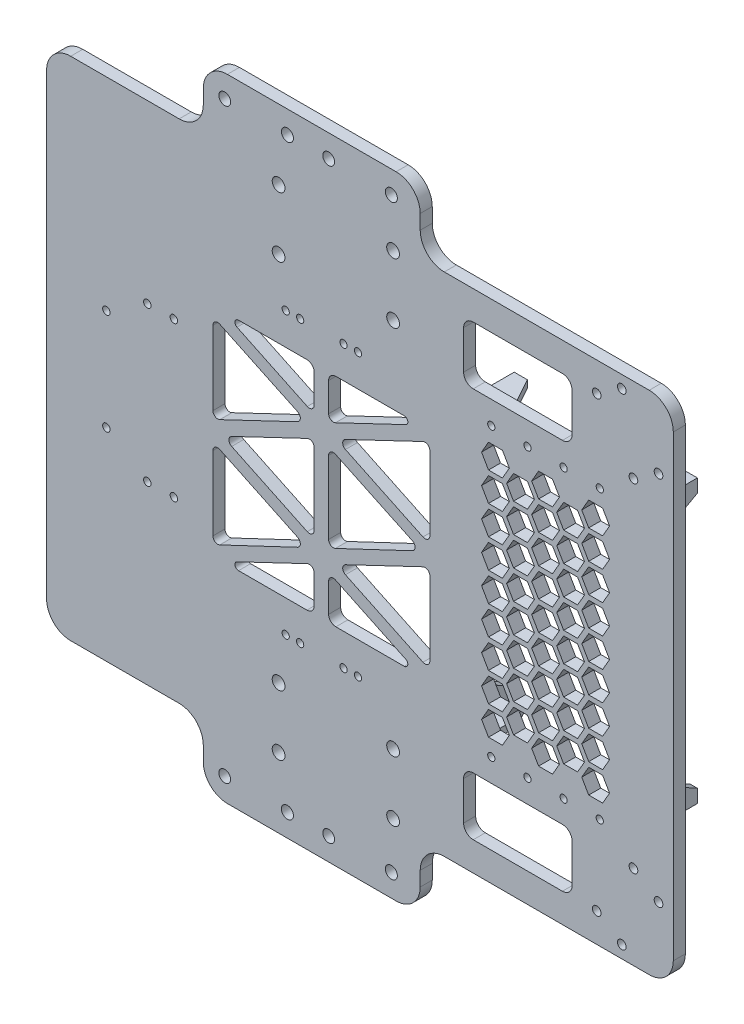
SolidWorks part; units mm, degrees
ref_plane "前视基准面" through (0, 0, 0) normal (0, 0, 1) x (1, 0, 0)
ref_plane "上视基准面" through (0, 0, 0) normal (0, 1, 0) x (1, 0, 0)
ref_plane "右视基准面" through (0, 0, 0) normal (1, 0, 0) x (0, 0, -1)
sketch "草图1" plane through (0, 0, 0) normal (0, 0, 1) x (1, 0, 0)
  line L2 (-130, 95) -> (-130, -95)
  line L3 (-120, -105) -> (-75, -105)
  line L4 (130, 95) -> (130, -95)
  line L5 (126.7518, 102.3765) -> (130, 105) construction
  line L6 (-130, -105) -> (-126.7518, -102.3765) construction
  line L9 (-65, -115) -> (-65, -121)
  line L10 (-55, -131) -> (15, -131)
  line L11 (25, -121) -> (25, -115)
  line L13 (35, -105) -> (120, -105)
  line L14 (126.7518, -102.3765) -> (130, -105) construction
  line L15 (-130, 105) -> (-126.7518, 102.3765) construction
  line L16 (-130, 0) -> (130, 0) construction
  line L17 (35, 105) -> (120, 105)
  line L18 (25, 121) -> (25, 115)
  line L19 (-55, 131) -> (15, 131)
  line L20 (-65, 115) -> (-65, 121)
  line L21 (-120, 105) -> (-75, 105)
  arc A1 (-120, -105) -> (-130, -95) centre (-120, -95) cw
  arc A3 (120, -105) -> (130, -95) centre (120, -95) ccw
  arc A8 (-65, -115) -> (-75, -105) centre (-75, -115) ccw
  arc A9 (25, -115) -> (35, -105) centre (35, -115) cw
  arc A10 (-55, -131) -> (-65, -121) centre (-55, -121) cw
  arc A11 (15, -131) -> (25, -121) centre (15, -121) ccw
  arc A12 (15, 131) -> (25, 121) centre (15, 121) cw
  arc A13 (-55, 131) -> (-65, 121) centre (-55, 121) ccw
  arc A14 (25, 115) -> (35, 105) centre (35, 115) ccw
  arc A15 (-65, 115) -> (-75, 105) centre (-75, 115) cw
  arc A16 (120, 105) -> (130, 95) centre (120, 95) cw
  arc A17 (-120, 105) -> (-130, 95) centre (-120, 95) ccw
  point P0 (0, 0)
  point P40 (25, -105)
  point P45 (25, 105)
  dimension "D2" = 10
  dimension "D3" = 65
  dimension "D4" = 10
  dimension "D5" = 105
  dimension "D7" = 10
  dimension "D8" = 10
  dimension "D10" = 10
  dimension "D12" = 10
  dimension "D13" = 105
  dimension "D18" = 90
  dimension "D19" = 6
extrude "凸台-拉伸1" add sketch "草图1" along normal blind 5
sketch "草图4" plane through (0, 0, 0) normal (0, 0, -1) x (-1, 0, 0)
  line L0 (-39, -47.5) -> (-39, -58.5)
  line L1 (-39, -58.5) -> (-50, -58.5)
  line L2 (-50, -58.5) -> (-50, -55.5)
  line L3 (-50, -55.5) -> (-42, -55.5)
  line L4 (-42, -55.5) -> (-42, -47.5)
  line L5 (-42, -47.5) -> (-39, -47.5)
  line L6 (-130, 0) -> (-25.5592, 0) construction
  line L7 (-130, -95) -> (-130, 95) construction
  line L10 (-130, -95) -> (-130, 95) construction
  dimension "D1" = 11
  dimension "D2" = 11
  dimension "D3" = 3
  dimension "D4" = 3
  dimension "D5" = 80
  dimension "D7" = 55.5
extrude "凸台-拉伸2" add sketch "草图4" along normal blind 20
sketch "草图5" plane through (0, -58.5, 0) normal (0, -1, 0) x (1, 0, 0)
  line L0 (50, -10) -> (44.5, -20)
  line L1 (50, -20) -> (50, 0) construction
  line L2 (50, -20) -> (39, -20) construction
  line L3 (44.5, -20) -> (50, -20)
  line L4 (50, -20) -> (50, -10)
  dimension "D1" = 10
  dimension "D2" = 5.5
extrude "切除-拉伸3" cut sketch "草图5" against normal blind 10
sketch "草图6" plane through (39, 0, 0) normal (-1, 0, 0) x (0, 0, 1)
  line L0 (-20, -53) -> (-10, -47.5)
  line L1 (-20, -58.5) -> (-20, -47.5) construction
  line L2 (-20, -47.5) -> (0, -47.5) construction
  line L3 (-10, -47.5) -> (-20, -47.5)
  line L4 (-20, -47.5) -> (-20, -53)
  dimension "D1" = 10
  dimension "D2" = 5.5
extrude "切除-拉伸4" cut sketch "草图6" against normal blind 10
ref_plane "基准面2" through (77, 0, 0) normal (1, 0, 0) x (0, 0, -1)
mirror "镜向1" about plane through (77, 0, 0) normal (1, 0, 0) of "凸台-拉伸2", "切除-拉伸4", "切除-拉伸3"
mirror "镜向2" about plane through (0, 0, 0) normal (0, 1, 0) of "镜向1"
sketch "草图7" plane through (0, 0, 0) normal (0, 0, -1) x (-1, 0, 0)
  line L4 (-112, -55.5) -> (-104, -55.5) construction
  line L5 (-112, 47.5) -> (-112, 55.5) construction
  line L6 (-112, 55.5) -> (-104, 55.5) construction
  line L7 (-92.013, 36) -> (-94.8997, 41)
  line L8 (-94.8997, 41) -> (-100.6732, 41)
  line L9 (-100.6732, 41) -> (-103.56, 36)
  line L10 (-103.56, 36) -> (-100.6732, 31)
  line L11 (-100.6732, 31) -> (-94.8997, 31)
  line L12 (-94.8997, 31) -> (-92.013, 36)
  line L13 (-77.0019, 36) -> (-97.7865, 36) construction
  line L14 (-74.1151, 31) -> (-71.2284, 36)
  line L15 (-71.2284, 36) -> (-74.1151, 41)
  line L16 (-74.1151, 41) -> (-79.8886, 41)
  line L17 (-79.8886, 41) -> (-82.7754, 36)
  line L18 (-82.7754, 36) -> (-79.8886, 31)
  line L19 (-79.8886, 31) -> (-74.1151, 31)
  line L20 (-92.013, 24) -> (-94.8997, 29)
  line L21 (-93.1677, 30) -> (-90.2809, 25)
  line L22 (-90.2809, 25) -> (-84.5074, 25)
  line L23 (-84.5074, 25) -> (-81.6207, 30)
  line L24 (-81.6207, 30) -> (-84.5074, 35)
  line L25 (-84.5074, 35) -> (-90.2809, 35)
  line L26 (-90.2809, 35) -> (-93.1677, 30)
  line L27 (-84.5074, 37) -> (-81.6207, 42)
  line L28 (-81.6207, 42) -> (-84.5074, 47)
  line L29 (-84.5074, 47) -> (-90.2809, 47)
  line L30 (-90.2809, 47) -> (-93.1677, 42)
  line L31 (-93.1677, 42) -> (-90.2809, 37)
  line L32 (-90.2809, 37) -> (-84.5074, 37)
  line L33 (-79.8886, 43) -> (-74.1151, 43)
  line L34 (-74.1151, 43) -> (-71.2284, 48)
  line L35 (-71.2284, 48) -> (-74.1151, 53)
  line L36 (-74.1151, 53) -> (-79.8886, 53)
  line L37 (-79.8886, 53) -> (-82.7754, 48)
  line L38 (-82.7754, 48) -> (-79.8886, 43)
  line L39 (-94.8997, 43) -> (-92.013, 48)
  line L40 (-92.013, 48) -> (-94.8997, 53)
  line L41 (-94.8997, 53) -> (-100.6732, 53)
  line L42 (-100.6732, 53) -> (-103.56, 48)
  line L43 (-103.56, 48) -> (-100.6732, 43)
  line L44 (-100.6732, 43) -> (-94.8997, 43)
  line L45 (-72.3831, 42) -> (-69.4963, 37)
  line L46 (-69.4963, 37) -> (-63.7228, 37)
  line L47 (-63.7228, 37) -> (-60.8361, 42)
  line L48 (-60.8361, 42) -> (-63.7228, 47)
  line L49 (-63.7228, 47) -> (-69.4963, 47)
  line L50 (-69.4963, 47) -> (-72.3831, 42)
  line L51 (-94.8997, 29) -> (-100.6732, 29)
  line L52 (-100.6732, 29) -> (-103.56, 24)
  line L53 (-103.56, 24) -> (-100.6732, 19)
  line L54 (-100.6732, 19) -> (-94.8997, 19)
  line L55 (-94.8997, 19) -> (-92.013, 24)
  line L56 (-93.1677, 18) -> (-90.2809, 13)
  line L57 (-90.2809, 13) -> (-84.5074, 13)
  line L58 (-84.5074, 13) -> (-81.6207, 18)
  line L59 (-81.6207, 18) -> (-84.5074, 23)
  line L60 (-84.5074, 23) -> (-90.2809, 23)
  line L61 (-90.2809, 23) -> (-93.1677, 18)
  line L62 (-74.1151, 19) -> (-71.2284, 24)
  line L63 (-71.2284, 24) -> (-74.1151, 29)
  line L64 (-74.1151, 29) -> (-79.8886, 29)
  line L65 (-79.8886, 29) -> (-82.7754, 24)
  line L66 (-82.7754, 24) -> (-79.8886, 19)
  line L67 (-79.8886, 19) -> (-74.1151, 19)
  line L68 (-72.3831, 30) -> (-69.4963, 25)
  line L69 (-69.4963, 25) -> (-63.7228, 25)
  line L70 (-63.7228, 25) -> (-60.8361, 30)
  line L71 (-60.8361, 30) -> (-63.7228, 35)
  line L72 (-63.7228, 35) -> (-69.4963, 35)
  line L73 (-69.4963, 35) -> (-72.3831, 30)
  line L74 (-92.013, 12) -> (-94.8997, 17)
  line L75 (-94.8997, 17) -> (-100.6732, 17)
  line L76 (-100.6732, 17) -> (-103.56, 12)
  line L77 (-103.56, 12) -> (-100.6732, 7)
  line L78 (-100.6732, 7) -> (-94.8997, 7)
  line L79 (-94.8997, 7) -> (-92.013, 12)
  line L80 (-93.1677, 6) -> (-90.2809, 1)
  line L81 (-90.2809, 1) -> (-84.5074, 1)
  line L82 (-84.5074, 1) -> (-81.6207, 6)
  line L83 (-81.6207, 6) -> (-84.5074, 11)
  line L84 (-84.5074, 11) -> (-90.2809, 11)
  line L85 (-90.2809, 11) -> (-93.1677, 6)
  line L86 (-74.1151, 7) -> (-71.2284, 12)
  line L87 (-71.2284, 12) -> (-74.1151, 17)
  line L88 (-74.1151, 17) -> (-79.8886, 17)
  line L89 (-79.8886, 17) -> (-82.7754, 12)
  line L90 (-82.7754, 12) -> (-79.8886, 7)
  line L91 (-79.8886, 7) -> (-74.1151, 7)
  line L92 (-72.3831, 18) -> (-69.4963, 13)
  line L93 (-69.4963, 13) -> (-63.7228, 13)
  line L94 (-63.7228, 13) -> (-60.8361, 18)
  line L95 (-60.8361, 18) -> (-63.7228, 23)
  line L96 (-63.7228, 23) -> (-69.4963, 23)
  line L97 (-69.4963, 23) -> (-72.3831, 18)
  line L98 (-92.013, 0) -> (-94.8997, 5)
  line L99 (-94.8997, 5) -> (-100.6732, 5)
  line L100 (-100.6732, 5) -> (-103.56, 0)
  line L101 (-103.56, 0) -> (-100.6732, -5)
  line L102 (-100.6732, -5) -> (-94.8997, -5)
  line L103 (-94.8997, -5) -> (-92.013, 0)
  line L104 (-93.1677, -6) -> (-90.2809, -11)
  line L105 (-90.2809, -11) -> (-84.5074, -11)
  line L106 (-84.5074, -11) -> (-81.6207, -6)
  line L107 (-81.6207, -6) -> (-84.5074, -1)
  line L108 (-84.5074, -1) -> (-90.2809, -1)
  line L109 (-90.2809, -1) -> (-93.1677, -6)
  line L110 (-74.1151, -5) -> (-71.2284, 0)
  line L111 (-71.2284, 0) -> (-74.1151, 5)
  line L112 (-74.1151, 5) -> (-79.8886, 5)
  line L113 (-79.8886, 5) -> (-82.7754, 0)
  line L114 (-82.7754, 0) -> (-79.8886, -5)
  line L115 (-79.8886, -5) -> (-74.1151, -5)
  line L116 (-72.3831, 6) -> (-69.4963, 1)
  line L117 (-69.4963, 1) -> (-63.7228, 1)
  line L118 (-63.7228, 1) -> (-60.8361, 6)
  line L119 (-60.8361, 6) -> (-63.7228, 11)
  line L120 (-63.7228, 11) -> (-69.4963, 11)
  line L121 (-69.4963, 11) -> (-72.3831, 6)
  line L122 (-92.013, -12) -> (-94.8997, -7)
  line L123 (-94.8997, -7) -> (-100.6732, -7)
  line L124 (-100.6732, -7) -> (-103.56, -12)
  line L125 (-103.56, -12) -> (-100.6732, -17)
  line L126 (-100.6732, -17) -> (-94.8997, -17)
  line L127 (-94.8997, -17) -> (-92.013, -12)
  line L128 (-93.1677, -18) -> (-90.2809, -23)
  line L129 (-90.2809, -23) -> (-84.5074, -23)
  line L130 (-84.5074, -23) -> (-81.6207, -18)
  line L131 (-81.6207, -18) -> (-84.5074, -13)
  line L132 (-84.5074, -13) -> (-90.2809, -13)
  line L133 (-90.2809, -13) -> (-93.1677, -18)
  line L134 (-74.1151, -17) -> (-71.2284, -12)
  line L135 (-71.2284, -12) -> (-74.1151, -7)
  line L136 (-74.1151, -7) -> (-79.8886, -7)
  line L137 (-79.8886, -7) -> (-82.7754, -12)
  line L138 (-82.7754, -12) -> (-79.8886, -17)
  line L139 (-79.8886, -17) -> (-74.1151, -17)
  line L140 (-72.3831, -6) -> (-69.4963, -11)
  line L141 (-69.4963, -11) -> (-63.7228, -11)
  line L142 (-63.7228, -11) -> (-60.8361, -6)
  line L143 (-60.8361, -6) -> (-63.7228, -1)
  line L144 (-63.7228, -1) -> (-69.4963, -1)
  line L145 (-69.4963, -1) -> (-72.3831, -6)
  line L146 (-92.013, -24) -> (-94.8997, -19)
  line L147 (-94.8997, -19) -> (-100.6732, -19)
  line L148 (-100.6732, -19) -> (-103.56, -24)
  line L149 (-103.56, -24) -> (-100.6732, -29)
  line L150 (-100.6732, -29) -> (-94.8997, -29)
  line L151 (-94.8997, -29) -> (-92.013, -24)
  line L152 (-93.1677, -30) -> (-90.2809, -35)
  line L153 (-90.2809, -35) -> (-84.5074, -35)
  line L154 (-84.5074, -35) -> (-81.6207, -30)
  line L155 (-81.6207, -30) -> (-84.5074, -25)
  line L156 (-84.5074, -25) -> (-90.2809, -25)
  line L157 (-90.2809, -25) -> (-93.1677, -30)
  line L158 (-74.1151, -29) -> (-71.2284, -24)
  line L159 (-71.2284, -24) -> (-74.1151, -19)
  line L160 (-74.1151, -19) -> (-79.8886, -19)
  line L161 (-79.8886, -19) -> (-82.7754, -24)
  line L162 (-82.7754, -24) -> (-79.8886, -29)
  line L163 (-79.8886, -29) -> (-74.1151, -29)
  line L164 (-72.3831, -18) -> (-69.4963, -23)
  line L165 (-69.4963, -23) -> (-63.7228, -23)
  line L166 (-63.7228, -23) -> (-60.8361, -18)
  line L167 (-60.8361, -18) -> (-63.7228, -13)
  line L168 (-63.7228, -13) -> (-69.4963, -13)
  line L169 (-69.4963, -13) -> (-72.3831, -18)
  line L170 (-92.013, -36) -> (-94.8997, -31)
  line L171 (-94.8997, -31) -> (-100.6732, -31)
  line L172 (-100.6732, -31) -> (-103.56, -36)
  line L173 (-103.56, -36) -> (-100.6732, -41)
  line L174 (-100.6732, -41) -> (-94.8997, -41)
  line L175 (-94.8997, -41) -> (-92.013, -36)
  line L176 (-93.1677, -42) -> (-90.2809, -47)
  line L177 (-90.2809, -47) -> (-84.5074, -47)
  line L178 (-84.5074, -47) -> (-81.6207, -42)
  line L179 (-81.6207, -42) -> (-84.5074, -37)
  line L180 (-84.5074, -37) -> (-90.2809, -37)
  line L181 (-90.2809, -37) -> (-93.1677, -42)
  line L182 (-74.1151, -41) -> (-71.2284, -36)
  line L183 (-71.2284, -36) -> (-74.1151, -31)
  line L184 (-74.1151, -31) -> (-79.8886, -31)
  line L185 (-79.8886, -31) -> (-82.7754, -36)
  line L186 (-82.7754, -36) -> (-79.8886, -41)
  line L187 (-79.8886, -41) -> (-74.1151, -41)
  line L188 (-72.3831, -30) -> (-69.4963, -35)
  line L189 (-69.4963, -35) -> (-63.7228, -35)
  line L190 (-63.7228, -35) -> (-60.8361, -30)
  line L191 (-60.8361, -30) -> (-63.7228, -25)
  line L192 (-63.7228, -25) -> (-69.4963, -25)
  line L193 (-69.4963, -25) -> (-72.3831, -30)
  line L194 (-92.013, -48) -> (-94.8997, -43)
  line L195 (-94.8997, -43) -> (-100.6732, -43)
  line L196 (-100.6732, -43) -> (-103.56, -48)
  line L197 (-103.56, -48) -> (-100.6732, -53)
  line L198 (-100.6732, -53) -> (-94.8997, -53)
  line L199 (-94.8997, -53) -> (-92.013, -48)
  line L206 (-74.1151, -53) -> (-71.2284, -48)
  line L207 (-71.2284, -48) -> (-74.1151, -43)
  line L208 (-74.1151, -43) -> (-79.8886, -43)
  line L209 (-79.8886, -43) -> (-82.7754, -48)
  line L210 (-82.7754, -48) -> (-79.8886, -53)
  line L211 (-79.8886, -53) -> (-74.1151, -53)
  line L212 (-72.3831, -42) -> (-69.4963, -47)
  line L213 (-69.4963, -47) -> (-63.7228, -47)
  line L214 (-63.7228, -47) -> (-60.8361, -42)
  line L215 (-60.8361, -42) -> (-63.7228, -37)
  line L216 (-63.7228, -37) -> (-69.4963, -37)
  line L217 (-69.4963, -37) -> (-72.3831, -42)
  line L218 (-61.9908, 36) -> (-59.104, 31)
  line L219 (-61.9908, 48) -> (-59.104, 43)
  line L220 (-59.104, 43) -> (-53.3305, 43)
  line L221 (-53.3305, 43) -> (-50.4438, 48)
  line L222 (-50.4438, 48) -> (-53.3305, 53)
  line L223 (-53.3305, 53) -> (-59.104, 53)
  line L224 (-59.104, 53) -> (-61.9908, 48)
  line L225 (-59.104, 31) -> (-53.3305, 31)
  line L226 (-53.3305, 31) -> (-50.4438, 36)
  line L227 (-50.4438, 36) -> (-53.3305, 41)
  line L228 (-53.3305, 41) -> (-59.104, 41)
  line L229 (-59.104, 41) -> (-61.9908, 36)
  line L230 (-61.9908, 24) -> (-59.104, 19)
  line L231 (-59.104, 19) -> (-53.3305, 19)
  line L232 (-53.3305, 19) -> (-50.4438, 24)
  line L233 (-50.4438, 24) -> (-53.3305, 29)
  line L234 (-53.3305, 29) -> (-59.104, 29)
  line L235 (-59.104, 29) -> (-61.9908, 24)
  line L236 (-61.9908, 12) -> (-59.104, 7)
  line L237 (-59.104, 7) -> (-53.3305, 7)
  line L238 (-53.3305, 7) -> (-50.4438, 12)
  line L239 (-50.4438, 12) -> (-53.3305, 17)
  line L240 (-53.3305, 17) -> (-59.104, 17)
  line L241 (-59.104, 17) -> (-61.9908, 12)
  line L242 (-61.9908, 0) -> (-59.104, -5)
  line L243 (-59.104, -5) -> (-53.3305, -5)
  line L244 (-53.3305, -5) -> (-50.4438, 0)
  line L245 (-50.4438, 0) -> (-53.3305, 5)
  line L246 (-53.3305, 5) -> (-59.104, 5)
  line L247 (-59.104, 5) -> (-61.9908, 0)
  line L248 (-61.9908, -12) -> (-59.104, -17)
  line L249 (-59.104, -17) -> (-53.3305, -17)
  line L250 (-53.3305, -17) -> (-50.4438, -12)
  line L251 (-50.4438, -12) -> (-53.3305, -7)
  line L252 (-53.3305, -7) -> (-59.104, -7)
  line L253 (-59.104, -7) -> (-61.9908, -12)
  line L254 (-61.9908, -24) -> (-59.104, -29)
  line L255 (-59.104, -29) -> (-53.3305, -29)
  line L256 (-53.3305, -29) -> (-50.4438, -24)
  line L257 (-50.4438, -24) -> (-53.3305, -19)
  line L258 (-53.3305, -19) -> (-59.104, -19)
  line L259 (-59.104, -19) -> (-61.9908, -24)
  line L260 (-61.9908, -36) -> (-59.104, -41)
  line L261 (-59.104, -41) -> (-53.3305, -41)
  line L262 (-53.3305, -41) -> (-50.4438, -36)
  line L263 (-50.4438, -36) -> (-53.3305, -31)
  line L264 (-53.3305, -31) -> (-59.104, -31)
  line L265 (-59.104, -31) -> (-61.9908, -36)
  line L266 (-61.9908, -48) -> (-59.104, -53)
  line L267 (-59.104, -53) -> (-53.3305, -53)
  line L268 (-53.3305, -53) -> (-50.4438, -48)
  line L269 (-50.4438, -48) -> (-53.3305, -43)
  line L270 (-53.3305, -43) -> (-59.104, -43)
  line L271 (-59.104, -43) -> (-61.9908, -48)
  line L272 (-93.1677, -54) -> (-90.2809, -59) [skipped]
  line L273 (-90.2809, -59) -> (-84.5074, -59) [skipped]
  line L274 (-84.5074, -59) -> (-81.6207, -54) [skipped]
  line L275 (-81.6207, -54) -> (-84.5074, -49) [skipped]
  line L276 (-84.5074, -49) -> (-90.2809, -49) [skipped]
  line L277 (-90.2809, -49) -> (-93.1677, -54) [skipped]
  circle A0 centre (-97.7865, 36) radius 5 construction
  circle A1 centre (-77.0019, 36) radius 5 construction
  circle A2 centre (-87.3942, 30) radius 5 construction
  circle A3 centre (-87.3942, 42) radius 5 construction
  circle A4 centre (-77.0019, 48) radius 5 construction
  circle A5 centre (-97.7865, 48) radius 5 construction
  circle A6 centre (-66.6096, 42) radius 5 construction
  circle A7 centre (-56.2173, 48) radius 5 construction
  point P4 (-87.3942, 37)
  dimension "D1" = 2
  dimension "D3" = 10
  dimension "D4" = 10
  dimension "D5" = 2
  dimension "D7" = 10
  dimension "D11" = 10
  dimension "D14" = 10
  dimension "D15" = 10
  dimension "D20" = 10
  dimension "D2" = 2
  dimension "D6" = 2
  dimension "D8" = 2
  dimension "D9" = 2
  dimension "D10" = 2
  dimension "D12" = 2
  dimension "D13" = 2
  dimension "D16" = 2
  dimension "D17" = 2
  dimension "D19" = 2
  dimension "D21" = 9
  dimension "D22" = 2.5
  dimension "D23" = 2.5
  dimension "D24" = 8.44
  dimension "D18" = 8
extrude "切除-拉伸5" cut sketch "草图7" against normal blind 5
sketch "草图8" plane through (0, 0, 0) normal (0, 0, -1) x (-1, 0, 0)
  line L0 (-75.3677, 120) -> (-75.3677, -120)
  line L1 (-100.0285, 77.2863) -> (-100.0285, -77.2863)
  line L2 (-100.0285, 77.2863) -> (-75.3677, 120)
  line L3 (-100.0285, -77.2863) -> (-75.3677, -120)
  line L4 (-37.1297, 0) -> (-146.8562, 0) construction
  dimension "D1" = 30
  dimension "D2" = 30
  dimension "D3" = 120
  dimension "D4" = 120
sketch "草图9" plane through (0, 0, 0) normal (0, 0, -1) x (-1, 0, 0)
  line L0 (148.8518, 0) -> (-37.1297, 0) construction
  line L1 (-29, 41) -> (-29, 4)
  line L2 (-25, -45) -> (13, -45)
  line L3 (61, -41) -> (61, -4)
  line L4 (57, 45) -> (19, 45)
  line L14 (-29, 41) -> (9.8049, 22.5)
  line L15 (57, 0) -> (19, -18.1163)
  line L16 (130, 95) -> (130, -95) construction
  line L17 (63, 93) -> (118, 93)
  line L18 (63, 93) -> (63, 66)
  line L19 (63, 66) -> (118, 66)
  line L20 (118, 93) -> (118, 66)
  line L21 (75, 105) -> (120, 105) construction
  line L22 (63, -66) -> (118, -66)
  line L23 (118, -93) -> (118, -66)
  line L24 (63, -93) -> (118, -93)
  line L25 (63, -93) -> (63, -66)
  line L26 (-120, 105) -> (-35, 105) construction
  line L27 (-43, 93) -> (-88, 93)
  line L28 (-43, 93) -> (-43, 69)
  line L29 (-43, 69) -> (-88, 69)
  line L30 (-88, 93) -> (-88, 69)
  line L31 (-130, -95) -> (-130, 95) construction
  line L32 (-43, -69) -> (-88, -69)
  line L33 (-88, -93) -> (-88, -69)
  line L34 (-43, -93) -> (-88, -93)
  line L35 (-43, -93) -> (-43, -69)
  line L36 (-25, 45) -> (13, 26.8837)
  line L37 (-25, -45) -> (13, -26.8837)
  line L38 (61, 41) -> (22.0746, 22.5575)
  line L39 (-25.5359, 0) -> (13, -18.258)
  line L40 (57, 45) -> (19, 26.8837)
  line L41 (57, -45) -> (19, -26.8837)
  line L42 (16, 61.4977) -> (16, -60.5731) construction
  line L43 (13, 45) -> (13, 26.8837)
  line L44 (19, 45) -> (19, 26.8837)
  line L45 (13, 18.258) -> (13, -18.258)
  line L46 (9.8049, 22.5) -> (-29, 4)
  line L47 (19, 18.1163) -> (57, 0)
  line L48 (22.0746, 22.5575) -> (61, 4)
  line L49 (13, 18.258) -> (-25.5359, 0)
  line L50 (19, 18.1163) -> (19, -18.1163)
  line L51 (22.0746, -22.5575) -> (61, -41)
  line L52 (9.8049, -22.5) -> (-29, -41)
  line L53 (9.8049, -22.5) -> (-29, -4)
  line L54 (22.0746, -22.5575) -> (61, -4)
  line L55 (13, -26.8837) -> (13, -45)
  line L56 (19, -26.8837) -> (19, -45)
  line L57 (13, 45) -> (-25, 45)
  line L58 (-29, -4) -> (-29, -41)
  line L59 (19, -45) -> (57, -45)
  line L60 (61, 4) -> (61, 41)
  line L61 (-44, 41) -> (-44, -37.8122) construction
  dimension "D1" = 45
  dimension "D2" = 45
  dimension "D3" = 15
  dimension "D4" = 90
  dimension "D5" = 1
  dimension "D7" = 12
  dimension "D8" = 12
  dimension "D9" = 27
  dimension "D10" = 55
  dimension "D11" = 12
  dimension "D12" = 45
  dimension "D13" = 42
  dimension "D14" = 24
  dimension "D21" = 4
  dimension "D22" = 4
  dimension "D23" = 4
  dimension "D24" = 4
  dimension "D26" = 4
  dimension "D27" = 3
  dimension "D28" = 45
extrude "切除-拉伸6" cut sketch "草图9" against normal blind 5 contours L27 L30 L29 L28 | L34 L35 L32 L33 | L4 L44 L40 | L48 L60 L38 | L47 L50 L15 | L54 L51 L3 | L56 L59 L41 | L55 L37 L2 | L53 L58 L52 | L45 L49 L39 | L46 L14 L1 | L43 L57 L36 | L57 L36 L43 region at (16.065, 22.5, 0) region at (-0.3333, -38.9612, 0) region at (-48.0249, -22.5192, 0) region at (-31.6667, 38.9612, 0) region at (-31.6667, 0, 0) region at (65.5, 81, 0) region at (65.5, -81, 0) region at (-0.3333, 38.9612, 0) region at (-48.0249, 22.5192, 0) region at (-0.1547, 0, 0) region at (-31.6667, -38.9612, 0) region at (16.065, -22.5, 0)
fillet "圆角1" radius 4 8 edges at (43, -93, 2.5) (88, -69, 2.5) (43, -69, 2.5) (88, -93, 2.5) (88, 69, 2.5) (43, 69, 2.5) (43, 93, 2.5) (88, 93, 2.5)
fillet "圆角2" radius 1.5 4 edges at (25, -45, 2.5) (-57, -45, 2.5) (25, 45, 2.5) (-57, 45, 2.5)
fillet "圆角3" radius 2 22 edges at (29, -4, 2.5) (29, 4, 2.5) (-13, -18.258, 2.5) (-61, -41, 2.5) (-61, 4, 2.5) (-13, -26.8837, 2.5) (-13, 18.258, 2.5) (-61, -4, 2.5) (-22.0746, -22.5575, 2.5) (25.5359, 0, 2.5) (-22.0746, 22.5575, 2.5) (-61, 41, 2.5) (-19, 26.8837, 2.5) (-19, -26.8837, 2.5) (-19, -18.1163, 2.5) (29, -41, 2.5) (29, 41, 2.5) (-57, 0, 2.5) (-9.8049, -22.5, 2.5) (-13, 26.8837, 2.5) (-9.8049, 22.5, 2.5) (-19, 18.1163, 2.5)
fillet "圆角4" radius 3 4 edges at (-13, -45, 2.5) (-13, 45, 2.5) (-19, -45, 2.5) (-19, 45, 2.5)
sketch "草图10" plane through (0, 0, 0) normal (0, 0, -1) x (-1, 0, 0)
  line L0 (-37.1297, 0) -> (-146.8562, 0) construction
  line L1 (-37.1297, 0) -> (-146.8562, 0) construction
  circle A0 centre (-123.8743, 76.9597) radius 1.8 construction
  circle A1 centre (-113.4687, 70.0334) radius 1.8 construction
  circle A2 centre (-108.6364, 99.852) radius 1.8 construction
  circle A3 centre (-98.2308, 92.9256) radius 1.8 construction
  circle A4 centre (105.2101, 21) radius 1.55 construction
  circle A5 centre (88.2101, 32) radius 1.55 construction
  circle A6 centre (77.2101, 32) radius 1.55 construction
  circle A7 centre (33.75, 102) radius 2.65 construction
  circle A8 centre (33.75, 77) radius 2.65 construction
  circle A9 centre (-13.75, 77) radius 2.65 construction
  circle A10 centre (-13.75, 102) radius 2.65 construction
  circle A11 centre (-13.0267, 121.679) radius 2.5 construction
  circle A12 centre (56.0941, 121.679) radius 2.45 construction
  circle A13 centre (30.0941, 121.679) radius 2.5 construction
  circle A14 centre (12.9733, 121.679) radius 2.45 construction
  circle A15 centre (-123.8743, 76.9597) radius 1.8
  circle A16 centre (-113.4687, 70.0334) radius 1.8
  circle A17 centre (-108.6364, 99.852) radius 1.8
  circle A18 centre (-98.2308, 92.9256) radius 1.8
  circle A19 centre (105.2101, 21) radius 1.55
  circle A20 centre (88.2101, 32) radius 1.55
  circle A21 centre (77.2101, 32) radius 1.55
  circle A22 centre (33.75, 102) radius 2.65
  circle A23 centre (33.75, 77) radius 2.65
  circle A24 centre (-13.75, 77) radius 2.65
  circle A25 centre (-13.75, 102) radius 2.65
  circle A26 centre (-13.0267, 121.679) radius 2.5
  circle A27 centre (56.0941, 121.679) radius 2.45
  circle A28 centre (30.0941, 121.679) radius 2.5
  circle A29 centre (12.9733, 121.679) radius 2.45
  circle A30 centre (12.9733, -121.679) radius 2.45
  circle A31 centre (30.0941, -121.679) radius 2.5
  circle A32 centre (56.0941, -121.679) radius 2.45
  circle A33 centre (-13.0267, -121.679) radius 2.5
  circle A34 centre (-13.75, -102) radius 2.65
  circle A35 centre (-13.75, -77) radius 2.65
  circle A36 centre (33.75, -77) radius 2.65
  circle A37 centre (33.75, -102) radius 2.65
  circle A38 centre (77.2101, -32) radius 1.55
  circle A39 centre (88.2101, -32) radius 1.55
  circle A40 centre (105.2101, -21) radius 1.55
  circle A41 centre (-98.2308, -92.9256) radius 1.8
  circle A42 centre (-108.6364, -99.852) radius 1.8
  circle A43 centre (-113.4687, -70.0334) radius 1.8
  circle A44 centre (-123.8743, -76.9597) radius 1.8
  circle A45 centre (-99.5, 59.5) radius 1.5 construction
  circle A46 centre (-84.5, 59.5) radius 1.5 construction
  circle A47 centre (-69.5, 59.5) radius 1.5 construction
  circle A48 centre (-54.5, 59.5) radius 1.5 construction
  circle A49 centre (0.8061, 58.25) radius 1.5 construction
  circle A50 centre (6.8061, 58.25) radius 1.5 construction
  circle A51 centre (24.8061, 58.25) radius 1.5 construction
  circle A52 centre (30.8061, 58.25) radius 1.5 construction
  circle A53 centre (-99.5, 59.5) radius 1.5
  circle A54 centre (-84.5, 59.5) radius 1.5
  circle A55 centre (-69.5, 59.5) radius 1.5
  circle A56 centre (-54.5, 59.5) radius 1.5
  circle A57 centre (0.8061, 58.25) radius 1.5
  circle A58 centre (6.8061, 58.25) radius 1.5
  circle A59 centre (24.8061, 58.25) radius 1.5
  circle A60 centre (30.8061, 58.25) radius 1.5
  circle A61 centre (30.8061, -58.25) radius 1.5
  circle A62 centre (24.8061, -58.25) radius 1.5
  circle A63 centre (6.8061, -58.25) radius 1.5
  circle A64 centre (0.8061, -58.25) radius 1.5
  circle A65 centre (-54.5, -59.5) radius 1.5
  circle A66 centre (-69.5, -59.5) radius 1.5
  circle A67 centre (-84.5, -59.5) radius 1.5
  circle A68 centre (-99.5, -59.5) radius 1.5
extrude "切除-拉伸7" cut sketch "草图10" against normal through all
equation "\"45、\"=43.7672"
